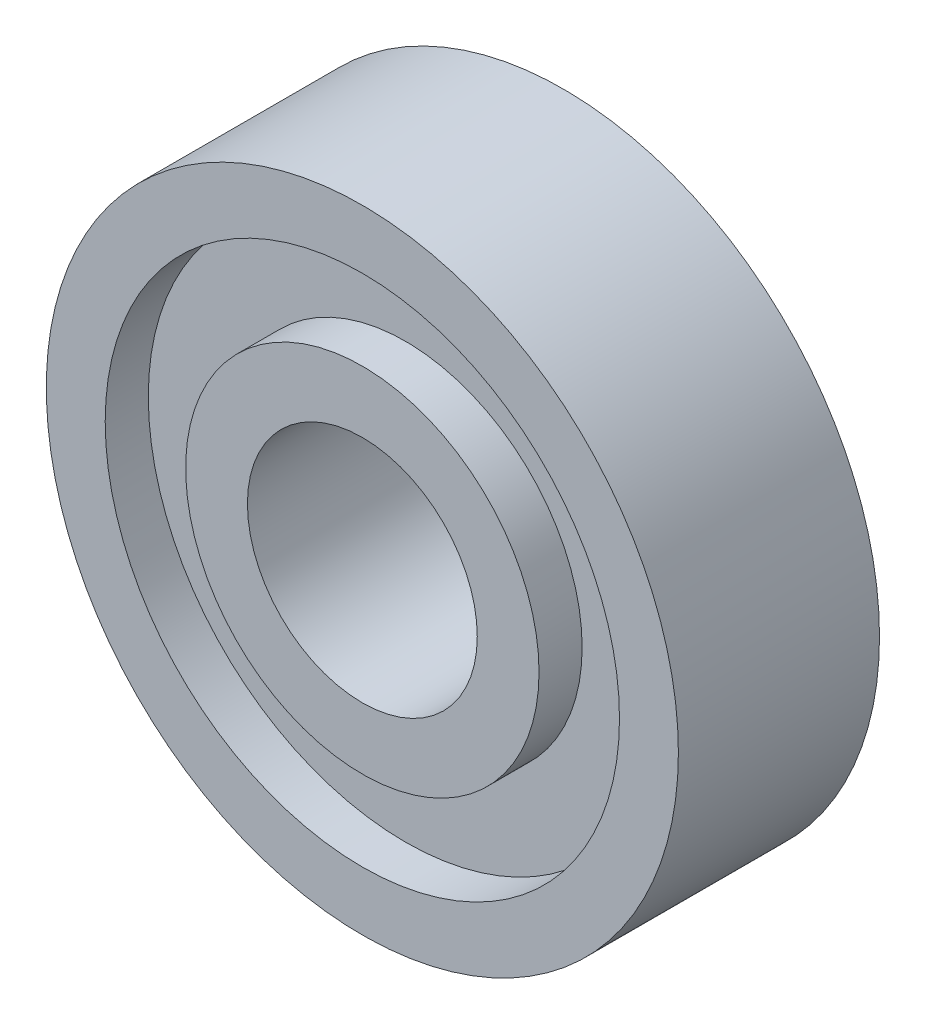
SolidWorks part; units mm, degrees
ref_plane "Alzado" through (0, 0, 0) normal (0, 0, 1) x (1, 0, 0)
ref_plane "Planta" through (0, 0, 0) normal (0, 1, 0) x (1, 0, 0)
ref_plane "Vista lateral" through (0, 0, 0) normal (1, 0, 0) x (0, 0, -1)
sketch "Croquis1" plane through (0, 0, 0) normal (0, 0, 1) x (1, 0, 0)
  circle A0 centre (0, 0) radius 4
  circle A1 centre (0, 0) radius 6.15
  circle A2 centre (0, 0) radius 8.95
  circle A3 centre (0, 0) radius 11
  dimension "D1" = 22
  dimension "D2" = 8
  dimension "D3" = 12.3
  dimension "D4" = 17.9
extrude "Saliente-Extruir1" add sketch "Croquis1" along normal blind 3.5 and the other way blind 3.5 contours A3 A2 | A1 A0 region at (-5.9761, 0, 0) region at (-10.6889, 0, 0)
extrude "Saliente-Extruir2" add sketch "Croquis1<3>" along normal blind 2 and the other way blind 2 contours A2 A1 region at (-8.6969, 0, 0)
sketch "Croquis1<3>" plane through (0, 0, 0) normal (0, 0, 1) x (1, 0, 0) same geometry as "Croquis1"
